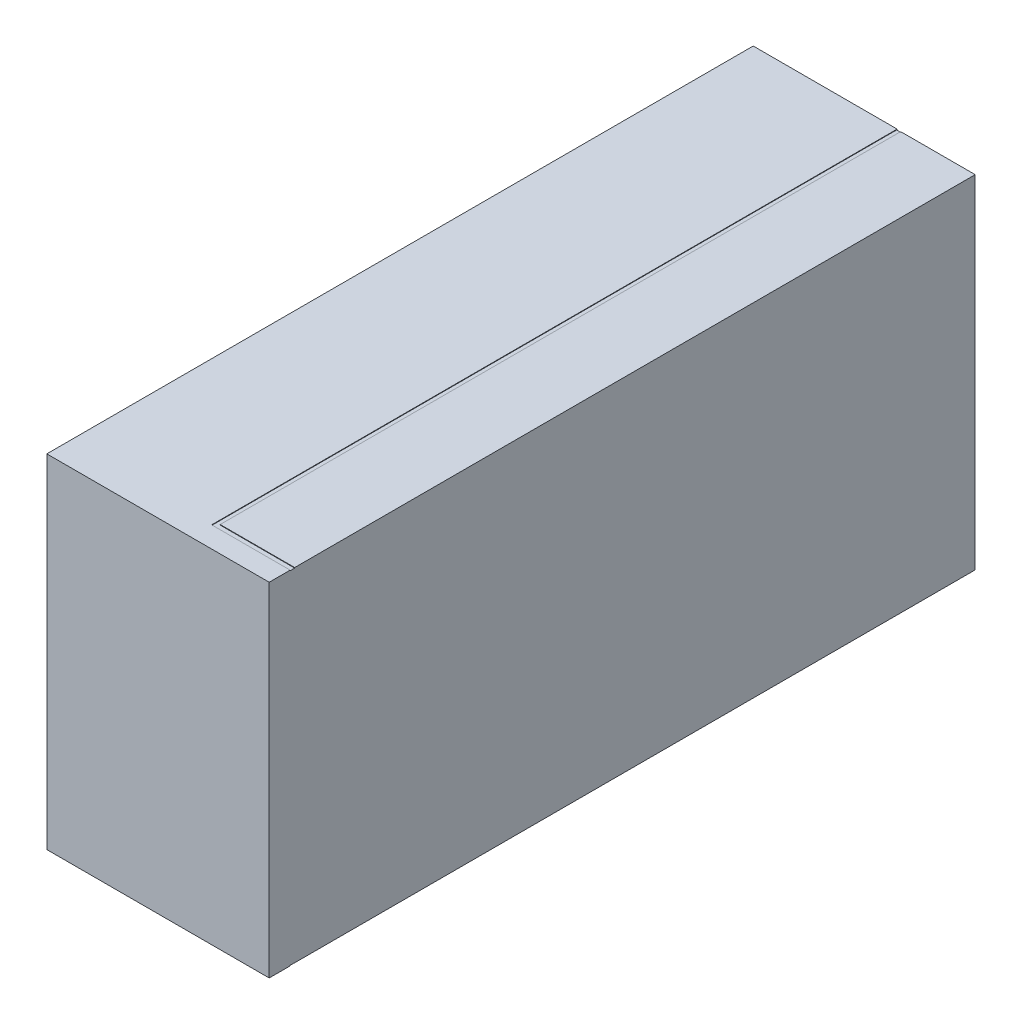
SolidWorks part; units mm, degrees
ref_plane "Front Plane" through (0, 0, 0) normal (0, 0, 1) x (1, 0, 0)
ref_plane "Top Plane" through (0, 0, 0) normal (0, 1, 0) x (1, 0, 0)
ref_plane "Right Plane" through (0, 0, 0) normal (1, 0, 0) x (0, 0, -1)
sketch "Sketch2" plane through (0, 0, 0) normal (1, 0, 0) x (0, 0, -1)
  line L1 (-33.75, -16.375) -> (33.75, -16.375)
  line L2 (-33.75, -16.375) -> (-33.75, 16.375)
  line L3 (-33.75, 16.375) -> (33.75, 16.375)
  line L4 (33.75, -16.375) -> (33.75, 16.375)
  line L5 (-33.75, -16.375) -> (33.75, 16.375) construction
  line L6 (-33.75, 16.375) -> (33.75, -16.375) construction
  point P0 (0, 0)
extrude "Boss-Extrude1" add sketch "Sketch2" along normal blind 21.25
sketch "Sketch3" plane through (0, 16.375, 0) normal (0, 1, 0) x (1, 0, 0)
  line L0 (21.25, 33.75) -> (13.75, 33.75) construction
  line L1 (21.25, 33.75) -> (0, 33.75) construction
  line L2 (21.25, -33.75) -> (21.25, -31.7471) construction
  line L3 (21.25, 33.75) -> (21.25, -33.75) construction
  line L4 (21.25, -31.7471) -> (13.75, -31.7471) construction
  line L5 (13.75, 33.75) -> (13.75, -31.7471)
  line L6 (13.75, -31.7471) -> (21.25, -31.7471)
  line L7 (13.75, 33.75) -> (13.751, 33.75)
extrude "Cut-Extrude3" cut sketch "Sketch3" against normal blind 0.05 and the other way through all
sketch "Sketch4" plane through (0, 0, -33.75) normal (0, 0, -1) x (-1, 0, 0)
  line L0 (-21.25, 16.325) -> (-13.75, 16.325) construction
  line L1 (-13.75, 16.325) -> (-13.75, -16.375)
  line L2 (-21.25, -16.375) -> (0, -16.375) construction
  line L3 (-13.75, -16.375) -> (-21.25, -16.375)
  line L4 (-21.25, -16.375) -> (-21.25, 16.325) construction
  line L5 (-13.75, 16.325) -> (-21.25, 16.325)
  line L6 (-21.25, 16.325) -> (-21.25, -16.375)
extrude "Cut-Extrude6" cut sketch "Sketch4" against normal blind 0.05
sketch "Sketch5" plane through (0, -16.375, 0) normal (0, -1, 0) x (-1, 0, 0)
  line L0 (-21.25, -33.75) -> (-21.25, -31.75) construction
  line L1 (-21.25, -33.75) -> (-21.25, 33.7) construction
  line L2 (-21.25, -31.75) -> (-13.75, -31.75)
  line L5 (-21.25, 33.7) -> (-13.75, 33.7) construction
  line L6 (-21.25, 33.7) -> (-21.25, -31.75)
  line L7 (-21.25, 33.7) -> (-13.75, 33.7)
  line L8 (-13.75, 33.7) -> (-13.75, -31.75)
extrude "Cut-Extrude7" cut sketch "Sketch5" against normal blind 0.05
sketch "Sketch6" plane through (0, 16.325, 0) normal (0, 1, 0) x (1, 0, 0)
  line L1 (21.25, 33.7) -> (14.1301, 33.7)
  line L2 (21.25, 33.7) -> (21.25, -31.3137)
  line L3 (21.25, -31.3137) -> (14.1301, -31.3137)
  line L4 (14.1301, 33.7) -> (14.1301, -31.3137)
extrude "Boss-Extrude9" add sketch "Sketch6" along normal blind 0.05
sketch "Sketch15" plane through (0, 0, -33.7) normal (0, 0, -1) x (-1, 0, 0)
  line L0 (-21.25, -16.325) -> (-13.75, -16.325) construction
  line L1 (-21.25, 16.375) -> (-14.3549, 16.375)
  line L2 (-21.25, 16.375) -> (-21.25, -16.325)
  line L3 (-21.25, -16.325) -> (-14.3549, -16.325)
  line L4 (-14.3549, 16.375) -> (-14.3549, -16.325)
extrude "Boss-Extrude14" add sketch "Sketch15" along normal blind 0.01
sketch "Sketch16" plane through (0, -16.325, 0) normal (0, -1, 0) x (-1, 0, 0)
  line L1 (-21.25, 33.71) -> (-14.1102, 33.71)
  line L2 (-21.25, 33.71) -> (-21.25, -31.3361)
  line L3 (-21.25, -31.3361) -> (-14.1102, -31.3361)
  line L4 (-14.1102, 33.71) -> (-14.1102, -31.3361)
extrude "Boss-Extrude15" add sketch "Sketch16" along normal blind 0.01
sketch "Sketch18" plane through (0, 0, 0) normal (-1, 0, 0) x (0, 0, 1)
  line L1 (-32.2671, 12.9229) -> (-20.2671, 12.9229)
  line L2 (-32.2671, 12.9229) -> (-32.2671, -2.0771)
  line L3 (-32.2671, -2.0771) -> (-20.2671, -2.0771)
  line L4 (-20.2671, 12.9229) -> (-20.2671, -2.0771)
extrude "Cut-Extrude14" cut sketch "Sketch18" against normal blind 3 draft 30 contours L2 L1 L4 L3
sketch "Sketch19" plane through (3, 0, 0) normal (-1, 0, 0) x (0, 0, 1)
  line L1 (-29.9923, 10.1849) -> (-22.4837, 10.1849)
  line L2 (-29.9923, 10.1849) -> (-29.9923, 6.9129)
  line L3 (-29.9923, 6.9129) -> (-22.4837, 6.9129)
  line L4 (-22.4837, 10.1849) -> (-22.4837, 6.9129)
extrude "Boss-Extrude16" add sketch "Sketch19" along normal blind 3 contours L2 L1 L4 L3
sketch "Sketch21" plane through (0, 0, -33.75) normal (0, 0, -1) x (-1, 0, 0)
  line L0 (-13.75, -16.375) -> (-10.25, -16.375) construction
  line L1 (-13.75, -16.375) -> (0, -16.375) construction
  line L2 (-10.25, -16.375) -> (-10.25, -10.875) construction
  circle A0 centre (-10.25, -10.875) radius 2.5
extrude "Cut-Extrude17" cut sketch "Sketch21" against normal blind 2 draft 35
